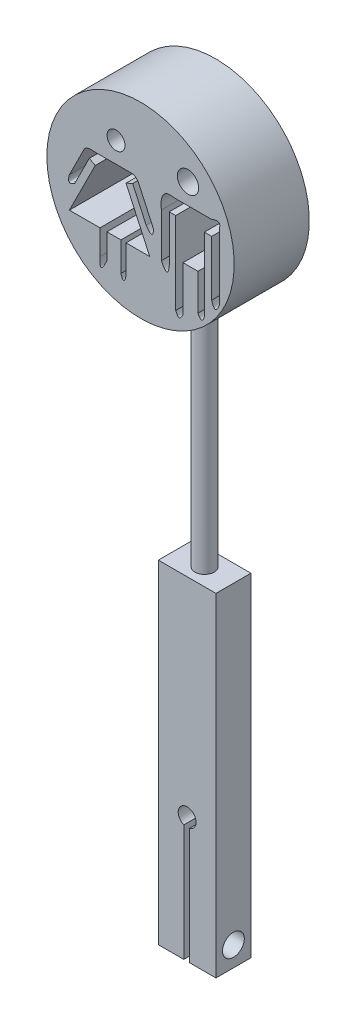
SolidWorks part; units mm, degrees
material "3003 Alloy"
ref_plane "Front Plane" through (0, 0, 0) normal (0, 0, 1) x (1, 0, 0)
ref_plane "Top Plane" through (0, 0, 0) normal (0, 1, 0) x (1, 0, 0)
ref_plane "Right Plane" through (0, 0, 0) normal (1, 0, 0) x (0, 0, -1)
sketch "Sketch1" plane through (0, 0, 0) normal (0, 0, 1) x (1, 0, 0)
  line L1 (-40.5563, 33.5822) -> (-34.1086, 33.5822)
  line L2 (-40.5563, 33.5822) -> (-40.5563, -3.6969)
  line L3 (-40.5563, -3.6969) -> (-34.1086, -3.6969)
  line L4 (-34.1086, 33.5822) -> (-34.1086, -3.6969)
extrude "Boss-Extrude1" add sketch "Sketch1" along normal blind 3.9133 and the other way blind 0.0001 contours L2 L1 L4 L3
sketch "Sketch4" plane through (0, 33.5822, 0) normal (0, 1, 0) x (1, 0, 0)
  line L5 (-40.5563, -1.9566) -> (-34.1086, -1.9566) construction
  line L6 (-40.5563, -3.9133) -> (-40.5563, 0.0001) construction
  line L7 (-34.1086, -3.9133) -> (-34.1086, 0.0001) construction
  line L8 (-37.3324, 0.0001) -> (-37.3324, -3.9133) construction
  line L9 (-40.5563, 0.0001) -> (-34.1086, 0.0001) construction
  line L10 (-40.5563, -3.9133) -> (-34.1086, -3.9133) construction
  circle A0 centre (-37.3324, -1.9566) radius 1.069
extrude "Boss-Extrude2" add sketch "Sketch4" along normal blind 37.846
sketch "Sketch9" plane through (0, 33.5822, 0) normal (0, 1, 0) x (1, 0, 0)
  line L0 (-37.3324, -0.8877) -> (-37.3324, -3.0256)
  circle A0 centre (-37.3324, -1.9566) radius 1.069 construction
  circle A1 centre (-37.3324, -1.9566) radius 1.069 construction
sketch "Sketch12" plane through (16.0168, 0, -0.0001) normal (0, 0, -1) x (-1, 0, 0)
  circle A0 centre (54.0734, 70.9914) radius 10.484
extrude "Boss-Extrude6" add sketch "Sketch12" along normal blind 0.0003 and the other way blind 8.4072 contours A0
sketch "Sketch13" plane through (4.6499, 0, -0.0004) normal (0, 0, -1) x (-1, 0, 0)
  line L0 (34.7414, 74.0835) -> (39.0314, 74.0835)
  line L1 (40.3741, 72.1841) -> (40.3741, 67.2719)
  line L2 (39.4899, 67.2719) -> (39.4899, 72.4461)
  line L3 (39.4899, 72.4461) -> (38.7694, 72.4461)
  line L4 (38.7694, 72.4461) -> (38.7694, 63.2438)
  line L5 (37.9507, 63.2438) -> (37.9507, 68.2871)
  line L6 (37.9507, 68.2871) -> (36.2805, 68.2871)
  line L7 (36.2805, 68.2871) -> (36.2805, 64.2263)
  line L8 (35.5601, 64.2263) -> (35.5601, 72.4461)
  line L9 (35.5601, 72.4461) -> (34.7414, 72.4461)
  line L10 (34.7414, 72.4461) -> (34.7414, 66.2567)
  line L11 (33.8572, 66.2567) -> (33.8572, 73.7233)
  line L12 (43.5251, 74.0835) -> (47.9896, 74.0835)
  line L13 (42.8927, 73.4647) -> (41.2615, 69.9075)
  line L14 (42.0771, 69.8559) -> (43.5861, 73.1467)
  line L15 (43.5861, 73.1467) -> (44.3286, 72.8062)
  line L16 (44.3286, 72.8062) -> (41.6743, 67.0178)
  line L17 (41.6743, 67.0178) -> (44.3286, 67.0178)
  line L18 (44.3286, 67.0178) -> (44.3286, 63.7678)
  line L19 (44.9017, 63.7678) -> (44.9017, 67.0178)
  line L20 (44.9017, 67.0178) -> (46.4643, 67.0178)
  line L21 (46.4643, 67.0178) -> (46.4643, 64.2263)
  line L22 (47.2456, 64.2263) -> (47.2456, 67.0178)
  line L23 (47.2456, 67.0178) -> (50.6684, 67.0178)
  line L24 (50.6684, 67.0178) -> (47.7664, 72.8062)
  line L25 (47.7664, 72.8062) -> (48.4456, 73.1467)
  line L26 (48.4456, 73.1467) -> (50.0672, 69.912)
  line L27 (50.6684, 70.4511) -> (48.957, 73.8648)
  circle A0 centre (37.39, 76.3984) radius 1.1955
  circle A1 centre (45.4452, 76.3984) radius 1.0001
  spline S0 degree 2 poles (39.0314, 74.0835) (40.6116, 74.4086) (40.3741, 72.1841) knots 0 0 0 1 1 1
  spline S1 degree 2 poles (40.3741, 67.2719) (39.6003, 65.6804) (39.4899, 67.2719) knots 0 0 0 1 1 1
  spline S2 degree 3 poles (38.7694, 63.2438) (38.6401, 62.9845) (38.3774, 62.4577) (38.0944, 62.9792) (37.9507, 63.2438) knots 0 0 0 0 0.492423 1 1 1 1
  spline S3 degree 2 poles (36.2805, 64.2263) (35.8385, 63.305) (35.5601, 64.2263) knots 0 0 0 1 1 1
  spline S4 degree 2 poles (34.7414, 66.2567) (34.3689, 64.8798) (33.8572, 66.2567) knots 0 0 0 1 1 1
  spline S5 degree 2 poles (33.8572, 73.7233) (33.677, 74.5256) (34.7414, 74.0835) knots 0 0 0 1 1 1
  spline S6 degree 3 poles (43.5251, 74.0835) (43.2364, 73.9608) (43.0256, 73.7545) (42.8927, 73.4647) knots 0 0 0 0 1 1 1 1
  spline S7 degree 2 poles (41.2615, 69.9075) (41.2633, 68.6724) (42.0771, 69.8559) knots 0 0 0 1 1 1
  spline S8 degree 2 poles (44.3286, 63.7678) (44.5981, 62.7198) (44.9017, 63.7678) knots 0 0 0 1 1 1
  spline S9 degree 2 poles (46.4643, 64.2263) (47.3453, 62.2446) (47.2456, 64.2263) knots 0 0 0 1 1 1
  spline S10 degree 2 poles (50.0672, 69.912) (51.0205, 69.2694) (50.6684, 70.4511) knots 0 0 0 1 1 1
  spline S11 degree 2 poles (48.957, 73.8648) (48.5141, 74.1732) (47.9896, 74.0835) knots 0 0 0 1 1 1
extrude "Cut-Extrude4" cut sketch "Sketch13" against normal through all both and the other way through all contours A1 | S11 L12 S6 L13 S7 L14 L15 L16 L17 L18 S8 L19 L20 L21 S9 L22 L23 L24 L25 L26 S10 L27 | S5 L0 S0 L1 S1 L2 L3 L4 S2 L5 L6 L7 S3 L8 L9 L10 S4 L11 | A0
sketch "Sketch14" plane through (0, 0, 0) normal (0, 0, 1) x (1, 0, 0)
  circle A0 centre (-37.3324, 10.2805) radius 1
extrude "Cut-Extrude5" cut sketch "Sketch14" against normal through all both and the other way through all
sketch "Sketch16" plane through (0, 0, 3.9133) normal (0, 0, 1) x (1, 0, 0)
  line L0 (-40.5563, -0.8809) -> (-34.225, -0.8809) construction
  line L1 (-40.5563, 33.5822) -> (-40.5563, -3.6969) construction
  line L2 (-37.3906, -0.8809) -> (-37.3906, 9.0926) construction
  line L4 (-37.7025, -8.0806) -> (-37.0787, -8.0806)
  line L5 (-37.7025, -8.0806) -> (-37.7025, 9.5624)
  line L6 (-37.7025, 9.5624) -> (-37.0787, 9.5624)
  line L7 (-37.0787, -8.0806) -> (-37.0787, 9.5624)
  line L8 (-37.7025, -8.0806) -> (-37.0787, 9.5624) construction
  line L9 (-37.7025, 9.5624) -> (-37.0787, -8.0806) construction
  point P6 (-37.3906, 0.7409)
extrude "Cut-Extrude6" cut sketch "Sketch16" against normal through all both
sketch "Sketch17" plane through (-40.5563, 0, 0) normal (-1, 0, 0) x (0, 0, 1)
  line L0 (-0.0001, -1.4575) -> (3.9133, -1.4575) construction
  line L1 (-0.0001, 33.5822) -> (-0.0001, -3.6969) construction
  line L2 (3.9133, 33.5822) -> (3.9133, -3.6969) construction
  line L3 (1.9566, -1.4575) -> (1.9566, -3.6969) construction
  line L4 (-0.0001, -3.6969) -> (3.9133, -3.6969) construction
  circle A0 centre (1.9566, -1.4575) radius 1.2192
extrude "Cut-Extrude7" cut sketch "Sketch17" against normal through all both and the other way through all
ref_axis "P-axis" through (-37.3324, 10.2805, -30.467) along (0, 0, 1)
